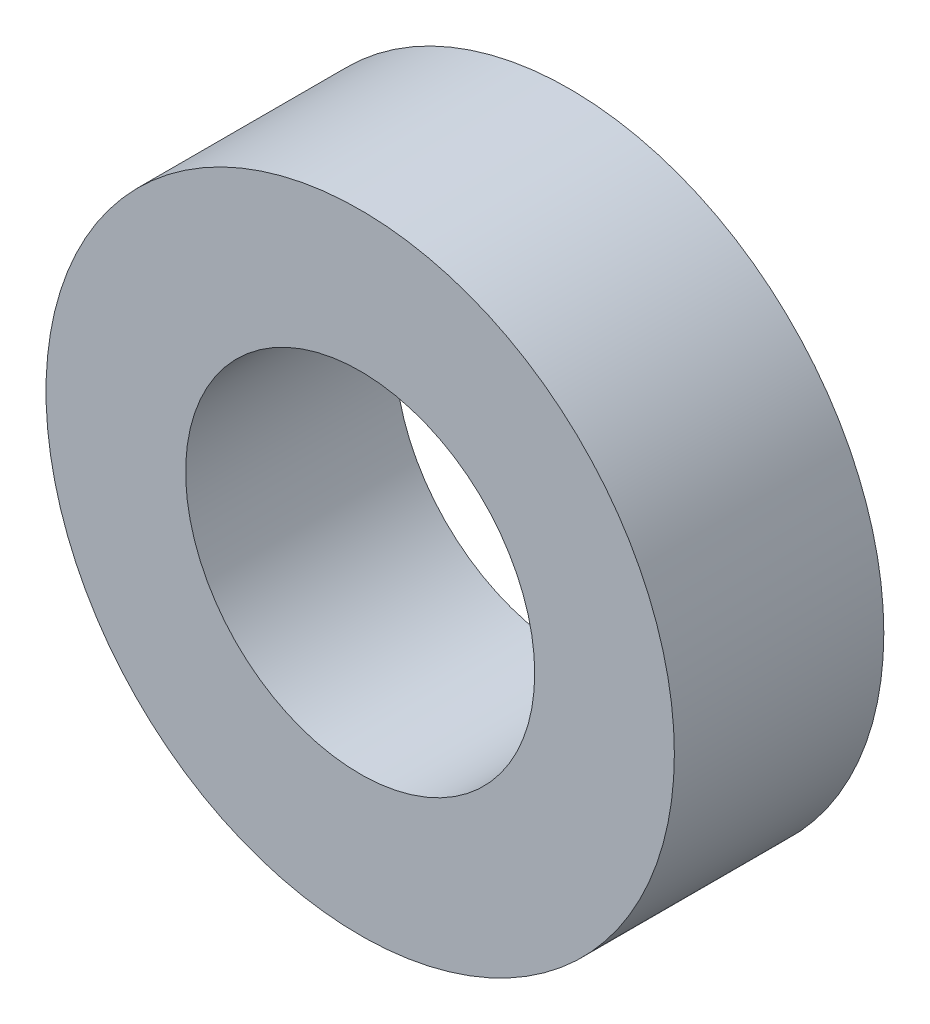
SolidWorks part; units mm, degrees
ref_plane "前视基准面" through (0, 0, 0) normal (0, 0, 1) x (1, 0, 0)
ref_plane "上视基准面" through (0, 0, 0) normal (0, 1, 0) x (1, 0, 0)
ref_plane "右视基准面" through (0, 0, 0) normal (1, 0, 0) x (0, 0, -1)
sketch "草图1" plane through (0, 0, 0) normal (0, 0, 1) x (1, 0, 0)
  circle A0 centre (0, 0) radius 2.5
  circle A1 centre (0, 0) radius 4.5
  dimension "D1" = 5
  dimension "D2" = 9
extrude "凸台-拉伸1" add sketch "草图1" along normal blind 3
